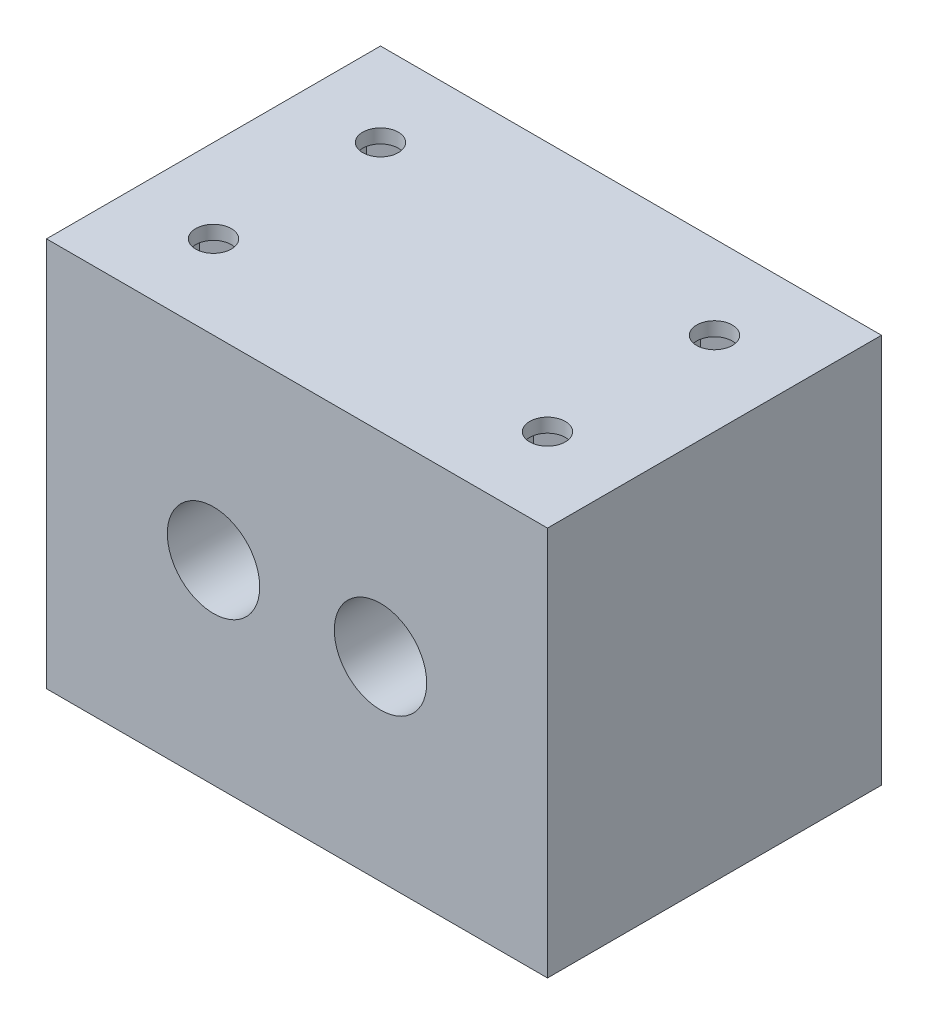
SolidWorks part; units mm, degrees
ref_plane "Front Plane" through (0, 0, 0) normal (0, 0, 1) x (1, 0, 0)
ref_plane "Top Plane" through (0, 0, 0) normal (0, 1, 0) x (1, 0, 0)
ref_plane "Right Plane" through (0, 0, 0) normal (1, 0, 0) x (0, 0, -1)
sketch "Sketch1" plane through (0, 0, 0) normal (0, 1, 0) x (1, 0, 0)
  line L0 (-22.5, 15) -> (-7.5, 0) construction
  line L1 (-7.5, -15) -> (7.5, -15)
  line L2 (-7.5, -15) -> (-7.5, 15)
  line L3 (-7.5, 15) -> (7.5, 15)
  line L4 (7.5, -15) -> (7.5, 15)
  line L5 (-7.5, -15) -> (7.5, 15) construction
  line L6 (-7.5, 15) -> (7.5, -15) construction
  line L7 (7.5, 15) -> (22.5, 15)
  line L8 (7.5, 15) -> (7.5, -15)
  line L9 (7.5, -15) -> (22.5, -15)
  line L10 (22.5, 15) -> (22.5, -15)
  line L11 (-7.5, 15) -> (-22.5, 15)
  line L12 (-7.5, 15) -> (-7.5, -15)
  line L13 (-7.5, -15) -> (-22.5, -15)
  line L14 (-22.5, 15) -> (-22.5, -15)
  line L15 (-7.5, 0) -> (-22.5, -15) construction
  line L16 (22.5, 15) -> (7.5, 0) construction
  line L17 (7.5, 0) -> (22.5, -15) construction
  line L19 (-15, 10.9352) -> (-17.975, 9.2176)
  line L20 (-17.975, 9.2176) -> (-17.975, 5.7824)
  line L21 (-17.975, 5.7824) -> (-15, 4.0648)
  line L22 (-15, 4.0648) -> (-12.025, 5.7824)
  line L23 (-12.025, 5.7824) -> (-12.025, 9.2176)
  line L24 (-12.025, 9.2176) -> (-15, 10.9352)
  line L25 (15, 10.9352) -> (12.025, 9.2176)
  line L26 (12.025, 9.2176) -> (12.025, 5.7824)
  line L27 (12.025, 5.7824) -> (15, 4.0648)
  line L28 (15, 4.0648) -> (17.975, 5.7824)
  line L29 (17.975, 5.7824) -> (17.975, 9.2176)
  line L30 (17.975, 9.2176) -> (15, 10.9352)
  line L31 (15, -4.0648) -> (12.025, -5.7824)
  line L32 (12.025, -5.7824) -> (12.025, -9.2176)
  line L33 (12.025, -9.2176) -> (15, -10.9352)
  line L34 (15, -10.9352) -> (17.975, -9.2176)
  line L35 (17.975, -9.2176) -> (17.975, -5.7824)
  line L36 (17.975, -5.7824) -> (15, -4.0648)
  line L37 (-15, -4.0648) -> (-17.975, -5.7824)
  line L38 (-17.975, -5.7824) -> (-17.975, -9.2176)
  line L39 (-17.975, -9.2176) -> (-15, -10.9352)
  line L40 (-15, -10.9352) -> (-12.025, -9.2176)
  line L41 (-12.025, -9.2176) -> (-12.025, -5.7824)
  line L42 (-12.025, -5.7824) -> (-15, -4.0648)
  circle A1 centre (-15, 7.5) radius 1.6
  circle A2 centre (15, 7.5) radius 1.6
  circle A3 centre (15, -7.5) radius 1.6
  circle A4 centre (-15, -7.5) radius 1.6
  circle A5 centre (-15, 7.5) radius 2.975 construction
  circle A6 centre (15, 7.5) radius 2.975 construction
  circle A7 centre (15, -7.5) radius 2.975 construction
  circle A8 centre (-15, -7.5) radius 2.975 construction
  point P0 (0, 0)
  dimension "D5" = 3.2
  dimension "D6" = 3.2
  dimension "D7" = 3.2
  dimension "D8" = 3.2
  dimension "D9" = 5.95
  dimension "D10" = 5.95
  dimension "D11" = 5.95
  dimension "D12" = 5.95
  dimension "D1" = 15
  dimension "D2" = 15
  dimension "D3" = 15
  dimension "D4" = 30
extrude "Boss-Extrude1" add sketch "Sketch1" along normal blind 5 contours L11 L14 L13 L2 L42 L41 L40 L39 L38 L37 L24 L23 L22 L21 L20 L19 | L1 L4 L3 L2 | L10 L7 L4 L9 L36 L35 L34 L33 L32 L31 L30 L29 L28 L27 L26 L25 | L41 L42 L37 L38 L39 L40 A4 | L23 L24 L19 L20 L21 L22 A1 | L29 L30 L25 L26 L27 L28 A2 | L35 L36 L31 L32 L33 L34 A3 region at (0, 0, 0) region at (-15, 0, 0) region at (15, 0, 0) region at (-13.5579, 0, -9.9977) region at (16.4421, 0, -9.9977) region at (16.4421, 0, 5.0023) region at (-13.5579, 0, 5.0023)
extrude "Cut-Extrude1" cut sketch "Sketch1<3>" along normal blind 2.5 from offset 1.25 contours L23 L24 L19 L20 L21 L22 A1 | L41 L42 L37 L38 L39 L40 A4 | L35 L36 L31 L32 L33 L34 A3 | L29 L30 L25 L26 L27 L28 A2 region at (-13.5579, 0, -9.9977) region at (16.4421, 0, -9.9977) region at (16.4421, 0, 5.0023) region at (-13.5579, 0, 5.0023)
sketch "Sketch1<3>" plane through (0, 0, 0) normal (0, 1, 0) x (1, 0, 0) same geometry as "Sketch1"
extrude "Boss-Extrude2" add sketch "Sketch1<4>" along normal blind 30 from surface contours L23 L24 L19 L20 L21 L22 A1 | L29 L30 L25 L26 L27 L28 A2 | L35 L36 L31 L32 L33 L34 A3 | L41 L42 L37 L38 L39 L40 A4 | L1 L4 L3 L2 | L11 L14 L13 L2 L42 L41 L40 L39 L38 L37 L24 L23 L22 L21 L20 L19 | L10 L7 L4 L9 L36 L35 L34 L33 L32 L31 L30 L29 L28 L27 L26 L25 region at (0, 0, 0) region at (-15, 0, 0) region at (15, 0, 0) region at (-13.5579, 0, -9.9977) region at (16.4421, 0, -9.9977) region at (16.4421, 0, 5.0023) region at (-13.5579, 0, 5.0023) starting at face at (0, 5, 0)
sketch "Sketch1<4>" plane through (0, 0, 0) normal (0, 1, 0) x (1, 0, 0) same geometry as "Sketch1"
sketch "Sketch5" plane through (0, 0, 15) normal (0, 0, 1) x (1, 0, 0)
  line L0 (22.5, 0) -> (-22.5, 0) construction
  line L1 (-22.5, 35) -> (-22.5, 0) construction
  line L2 (-22.5, 0) -> (22.5, 35) construction
  line L3 (-22.5, 35) -> (22.5, 0) construction
  line L4 (22.5, 35) -> (22.5, 0) construction
  line L5 (0, 17.5) -> (-7.5, 17.5) construction
  line L6 (0, 17.5) -> (7.5, 17.5) construction
  circle A0 centre (-7.5, 17.5) radius 4.15
  circle A1 centre (7.5, 17.5) radius 4.15
  dimension "D4" = 8.3
  dimension "D5" = 8.3
  dimension "D2" = 7.5
  dimension "D3" = 7.5
extrude "Cut-Extrude2" cut sketch "Sketch5" against normal through all
sketch "Sketch6" plane through (0, 35, 0) normal (0, 1, 0) x (1, 0, 0)
  line L1 (-15, 10.9352) -> (-17.975, 9.2176)
  line L2 (-17.975, 9.2176) -> (-17.975, 5.7824)
  line L3 (-17.975, 5.7824) -> (-15, 4.0648)
  line L4 (-15, 4.0648) -> (-12.025, 5.7824)
  line L5 (-12.025, 5.7824) -> (-12.025, 9.2176)
  line L6 (-12.025, 9.2176) -> (-15, 10.9352)
  line L7 (15, 10.9352) -> (12.025, 9.2176)
  line L8 (12.025, 9.2176) -> (12.025, 5.7824)
  line L9 (12.025, 5.7824) -> (15, 4.0648)
  line L10 (15, 4.0648) -> (17.975, 5.7824)
  line L11 (17.975, 5.7824) -> (17.975, 9.2176)
  line L12 (17.975, 9.2176) -> (15, 10.9352)
  line L13 (15, -4.0648) -> (12.025, -5.7824)
  line L14 (12.025, -5.7824) -> (12.025, -9.2176)
  line L15 (12.025, -9.2176) -> (15, -10.9352)
  line L16 (15, -10.9352) -> (17.975, -9.2176)
  line L17 (17.975, -9.2176) -> (17.975, -5.7824)
  line L18 (17.975, -5.7824) -> (15, -4.0648)
  line L19 (-15, -4.0648) -> (-17.975, -5.7824)
  line L20 (-17.975, -5.7824) -> (-17.975, -9.2176)
  line L21 (-17.975, -9.2176) -> (-15, -10.9352)
  line L22 (-15, -10.9352) -> (-12.025, -9.2176)
  line L23 (-12.025, -9.2176) -> (-12.025, -5.7824)
  line L24 (-12.025, -5.7824) -> (-15, -4.0648)
  circle A0 centre (-15, 7.5) radius 2.975 construction
  circle A1 centre (15, 7.5) radius 2.975 construction
  circle A2 centre (15, -7.5) radius 2.975 construction
  circle A3 centre (-15, -7.5) radius 2.975 construction
  dimension "D1" = 5.95
  dimension "D2" = 5.95
  dimension "D3" = 5.95
  dimension "D4" = 5.95
extrude "Cut-Extrude3" cut sketch "Sketch6" against normal blind 2.5 from offset 1.25 offset against normal yes
